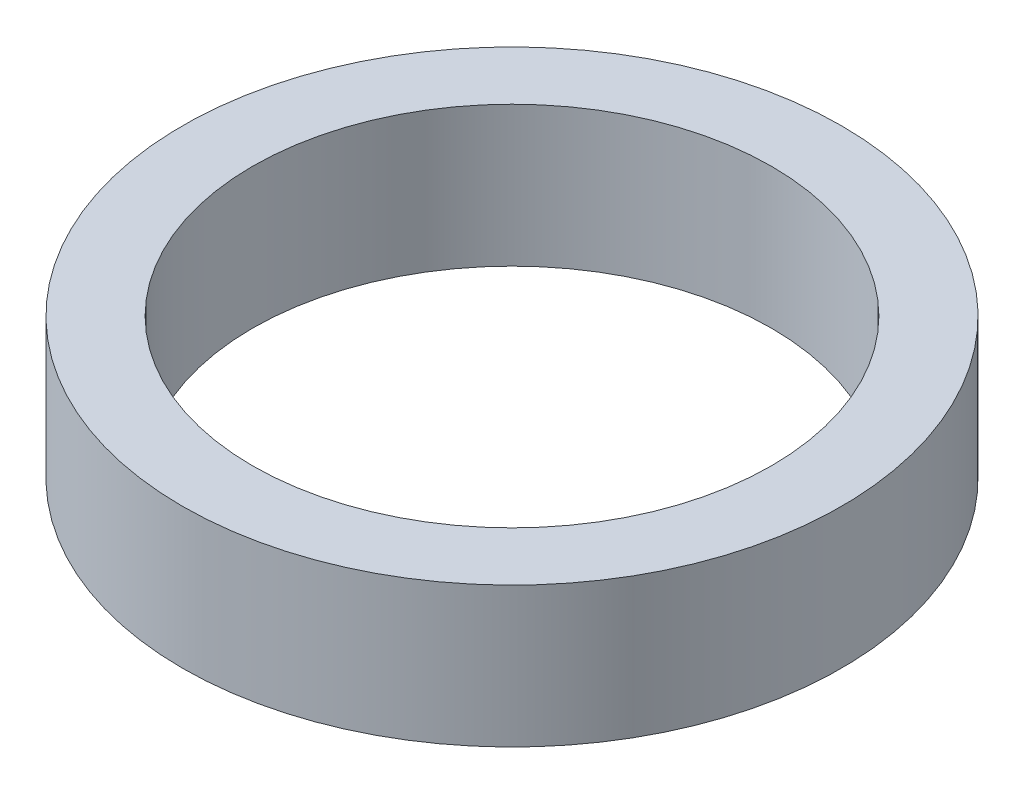
SolidWorks part; units mm, degrees
material "1023 Carbon Steel Sheet (SS)"
ref_plane "Front Plane" through (0, 0, 0) normal (0, 0, 1) x (1, 0, 0)
ref_plane "Top Plane" through (0, 0, 0) normal (0, 1, 0) x (1, 0, 0)
ref_plane "Right Plane" through (0, 0, 0) normal (1, 0, 0) x (0, 0, -1)
sketch "Sketch1" plane through (0, 0, 0) normal (0, 1, 0) x (1, 0, 0)
  circle A0 centre (0, 0) radius 29.845
  circle A1 centre (0, 0) radius 23.495
  dimension "D1" = 6.35
  dimension "D2" = 46.99
extrude "Boss-Extrude2" add sketch "Sketch1" along normal blind 12.7 contours A0 A1 region at (-29.0009, 0, 0)
sketch "Sketch2" plane through (0, 0, 0) normal (1, 0, 0) x (0, 0, -1)
  line L1 (0, 0) -> (0, 12.7)
  line L2 (29.845, 12.7) -> (-29.845, 12.7) construction
  line L6 (-29.845, 0) -> (29.845, 0) construction
  line L9 (-29.845, 0) -> (-23.495, 0) construction
  line L10 (-29.7809, 0) -> (-23.5591, 0)
  arc A2 (-29.7809, 0) -> (-23.5591, 0) centre (-26.67, -0.635) cw
  point P18 (-26.67, 0)
  point P19 (-26.67, 2.54)
  dimension "D1" = 3.175
  dimension "D2" = 2.54
revolve "Cut-Revolve1" cut sketch "Sketch2" angle 360 about L1
